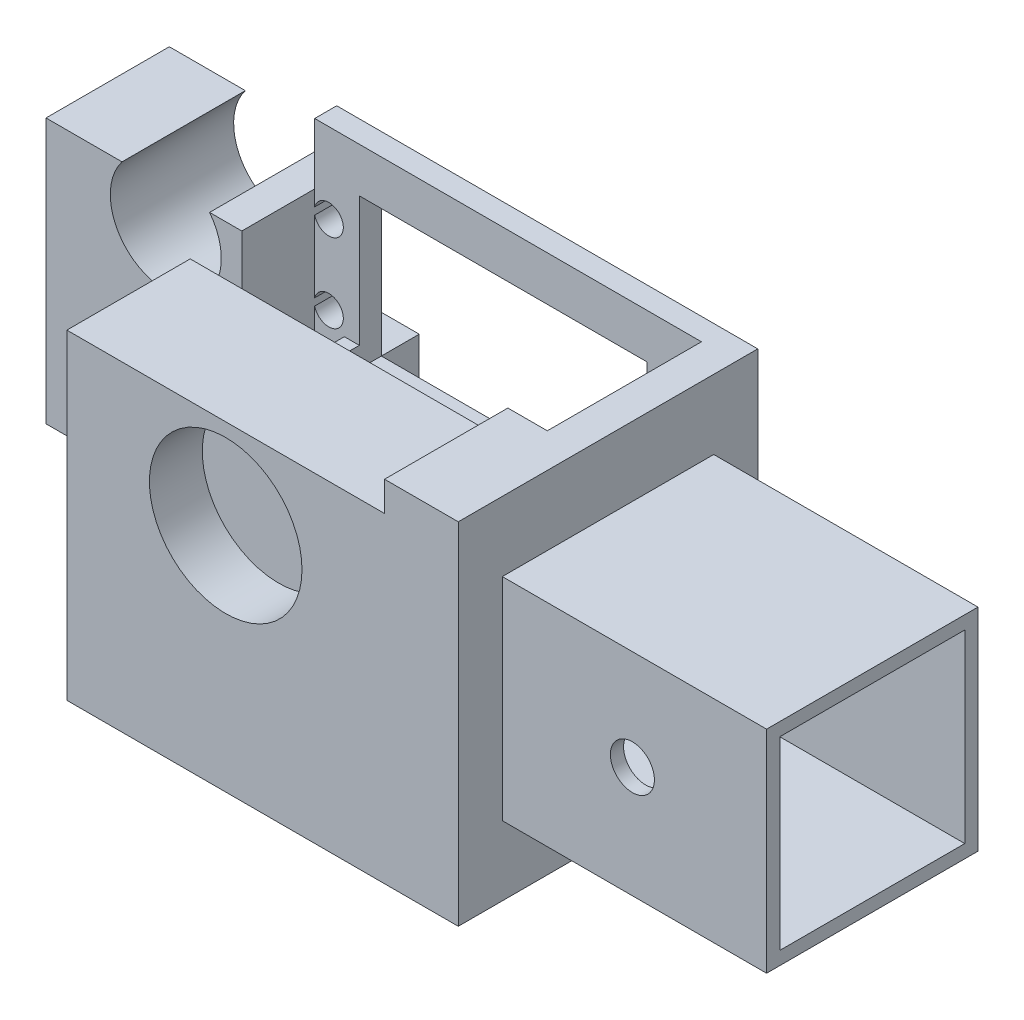
SolidWorks part; units mm, degrees
ref_plane "Front Plane" through (0, 0, 0) normal (0, 0, 1) x (1, 0, 0)
ref_plane "Top Plane" through (0, 0, 0) normal (0, 1, 0) x (1, 0, 0)
ref_plane "Right Plane" through (0, 0, 0) normal (1, 0, 0) x (0, 0, -1)
sketch "Sketch1" plane through (0, 0, 0) normal (0, 0, 1) x (1, 0, 0)
  line L1 (27.178, 17.2339) -> (-27.178, 17.2339)
  line L2 (27.178, 17.2339) -> (27.178, -17.2339)
  line L3 (27.178, -17.2339) -> (-27.178, -17.2339)
  line L4 (-27.178, 17.2339) -> (-27.178, -17.2339)
  line L5 (27.178, 17.2339) -> (-27.178, -17.2339) construction
  line L6 (27.178, -17.2339) -> (-27.178, 17.2339) construction
  line L7 (-27.178, 0) -> (-20.1041, 0) construction
  line L8 (-20.1041, 10.16) -> (-20.1041, -10.16) construction
  line L9 (0, 17.2339) -> (0, 10.16) construction
  line L10 (20.1041, 10.16) -> (-20.1041, 10.16) construction
  line L11 (-27.178, -5.1649) -> (-27.178, 5.1649) construction
  line L13 (20.1041, -10.16) -> (-20.1041, -10.16)
  line L14 (20.1041, -10.16) -> (20.1041, 10.16)
  line L15 (20.1041, 10.16) -> (-20.1041, 10.16)
  line L16 (-20.1041, -10.16) -> (-20.1041, 10.16)
  line L17 (20.1041, -10.16) -> (-20.1041, 10.16) construction
  line L18 (20.1041, 10.16) -> (-20.1041, -10.16) construction
  point P0 (0, 0)
  point P16 (0, 0)
extrude "Boss-Extrude1" add sketch "Sketch1" against normal up to surface (27.94 mm away)
sketch "Sketch2" plane through (0, 0, 0) normal (0, 0, 1) x (1, 0, 0)
  line L0 (20.1041, 10.16) -> (-20.1041, 10.16) construction
  line L1 (22.8981, -12.954) -> (-22.8981, -12.954)
  line L2 (22.8981, -12.954) -> (22.8981, 12.954)
  line L3 (22.8981, 12.954) -> (-22.8981, 12.954)
  line L4 (-22.8981, -12.954) -> (-22.8981, 12.954)
  line L5 (22.8981, -12.954) -> (-22.8981, 12.954) construction
  line L6 (22.8981, 12.954) -> (-22.8981, -12.954) construction
  line L7 (27.178, 17.2339) -> (-27.178, 17.2339)
  line L8 (27.178, 17.2339) -> (27.178, -17.2339)
  line L9 (27.178, -17.2339) -> (-27.178, -17.2339)
  line L10 (-27.178, 17.2339) -> (-27.178, -17.2339)
  line L11 (27.178, 17.2339) -> (-27.178, -17.2339) construction
  line L12 (27.178, -17.2339) -> (-27.178, 17.2339) construction
  line L13 (-20.1041, 10.16) -> (-20.1041, -10.16) construction
  point P0 (0, 0)
  point P6 (0, 0)
  dimension "D1" = 2.794
  dimension "D2" = 2.794
extrude "Cut-Extrude1" cut sketch "Sketch2" against normal offset from surface (24.765 mm away) 3.175 up to face at (0, 0, -27.94)
sketch "Sketch3" plane through (0, 0, -27.94) normal (0, 0, -1) x (-1, 0, 0)
  circle A0 centre (-25.146, 5.6769) radius 2.0497
  circle A1 centre (-25.146, -5.6769) radius 2.0955
  circle A2 centre (25.146, -5.6769) radius 2.0955
  circle A3 centre (25.146, 5.6769) radius 2.0955
extrude "Cut-Extrude2" cut sketch "Sketch3" against normal through all
sketch "Sketch4" plane through (22.8981, 0, 0) normal (1, 0, 0) x (0, 0, -1)
  line L0 (0, -12.954) -> (0, 12.954) construction
  line L1 (2.54, 4.7625) -> (21.59, 4.7625)
  line L2 (2.54, 4.7625) -> (2.54, -4.7625)
  line L3 (2.54, -4.7625) -> (21.59, -4.7625)
  line L4 (21.59, 4.7625) -> (21.59, -4.7625)
  point P4 (2.54, 0)
  dimension "D1" = 19.05
  dimension "D2" = 9.525
  dimension "D3" = 2.54
extrude "Cut-Extrude3" cut sketch "Sketch4" against normal blind 12.7
sketch "Sketch5" plane through (0, 0, 0) normal (0, 0, 1) x (1, 0, 0)
  line L1 (-22.8981, 12.954) -> (22.8981, 12.954)
  line L2 (-22.8981, 12.954) -> (-22.8981, -12.954)
  line L3 (-22.8981, -12.954) -> (22.8981, -12.954)
  line L4 (22.8981, 12.954) -> (22.8981, -12.954)
extrude "Boss-Extrude2" add sketch "Sketch5" along normal blind 2.54
sketch "Sketch6" plane through (0, 0, 2.54) normal (0, 0, 1) x (1, 0, 0)
  line L11 (-22.8981, -12.954) -> (22.8981, -12.954) construction
  line L12 (-12.7, -12.954) -> (12.7, -12.954)
  line L13 (-12.7, -12.954) -> (-12.7, -17.2339)
  line L14 (-12.7, -17.2339) -> (12.7, -17.2339)
  line L15 (12.7, -12.954) -> (12.7, -17.2339)
  line L16 (-27.178, -17.2339) -> (27.178, -17.2339) construction
  point P0 (0, -12.954)
  dimension "D1" = 25.4
extrude "Boss-Extrude3" add sketch "Sketch6" against normal up to surface (27.305 mm away) up to face at (0.0038, 0, -24.765)
sketch "Sketch7" plane through (0, 0, 2.54) normal (0, 0, 1) x (1, 0, 0)
  line L1 (-12.7, -17.2339) -> (12.7, -17.2339)
  line L2 (-12.7, -17.2339) -> (-12.7, -10.8839)
  line L3 (-12.7, -10.8839) -> (12.7, -10.8839)
  line L4 (12.7, -17.2339) -> (12.7, -10.8839)
  dimension "D1" = 25.4
  dimension "D2" = 6.35
extrude "Boss-Extrude4" add sketch "Sketch7" along normal blind 19.05
sketch "Sketch10" plane through (0, -10.8839, 0) normal (0, 1, 0) x (1, 0, 0)
  line L0 (22.8981, -2.54) -> (-22.8981, -2.54) construction
  line L1 (12.7, -21.59) -> (9.525, -21.59)
  line L2 (12.7, -21.59) -> (12.7, -2.54)
  line L3 (12.7, -2.54) -> (9.525, -2.54)
  line L4 (9.525, -21.59) -> (9.525, -2.54)
  line L6 (-12.7, -21.59) -> (-9.525, -21.59)
  line L7 (-12.7, -21.59) -> (-12.7, -2.54)
  line L8 (-12.7, -2.54) -> (-9.525, -2.54)
  line L9 (-9.525, -21.59) -> (-9.525, -2.54)
  dimension "D1" = 3.175
extrude "Boss-Extrude5" add sketch "Sketch10" along normal blind 19.05
chamfer "Chamfer1" distance 19.05 angle 45 2 edges at (-11.1125, 8.1661, 21.59) (11.1125, 8.1661, 21.59)
sketch "Sketch12" plane through (0, -17.2339, 0) normal (0, -1, 0) x (1, 0, 0)
  line L1 (-3.81, 3.81) -> (3.81, 3.81)
  line L2 (-3.81, 3.81) -> (-3.81, -27.94)
  line L3 (-3.81, -27.94) -> (3.81, -27.94)
  line L4 (3.81, 3.81) -> (3.81, -27.94)
  line L5 (-27.178, -27.94) -> (27.178, -27.94) construction
  point P8 (0, 3.81)
  dimension "D1" = 7.62
  dimension "D2" = 31.75
extrude "Boss-Extrude6" add sketch "Sketch12" along normal blind 3.175
sketch "Sketch13" plane through (0, 0, -27.94) normal (0, 0, -1) x (-1, 0, 0)
  line L0 (-20.1041, 10.16) -> (20.1041, 10.16) construction
  line L1 (20.7391, -10.795) -> (-20.7391, -10.795)
  line L2 (20.7391, -10.795) -> (20.7391, 10.795)
  line L3 (20.7391, 10.795) -> (-20.7391, 10.795)
  line L4 (-20.7391, -10.795) -> (-20.7391, 10.795)
  line L5 (20.7391, -10.795) -> (-20.7391, 10.795) construction
  line L6 (20.7391, 10.795) -> (-20.7391, -10.795) construction
  line L7 (-20.1041, -10.16) -> (-20.1041, 10.16) construction
  point P0 (0, 0)
  dimension "D1" = 0.635
  dimension "D2" = 0.635
extrude "Cut-Extrude7" cut sketch "Sketch13" against normal offset from surface (27.94 mm away) 2.54 up to face at (0, -1.251, 2.54)
sketch "Sketch14" plane through (-22.8981, 0, 0) normal (-1, 0, 0) x (0, 0, 1)
  line L0 (21.59, -10.8839) -> (21.59, -17.2339) construction
  line L5 (-24.765, 12.954) -> (-2.54, 12.954)
  line L6 (-24.765, 12.954) -> (-24.765, -7.874)
  line L7 (-24.765, -7.874) -> (-2.54, -7.874)
  line L8 (-2.54, 12.954) -> (-2.54, -7.874)
  line L9 (2.54, 12.954) -> (2.54, -12.954) construction
  line L10 (-24.765, -12.954) -> (2.54, -12.954) construction
  line L11 (-27.94, -20.4089) -> (21.59, -20.4089)
  line L12 (-27.94, -20.4089) -> (-27.94, -12.954)
  line L13 (-27.94, -12.954) -> (21.59, -12.954)
  line L14 (21.59, -20.4089) -> (21.59, -12.954)
  dimension "D1" = 5.08
  dimension "D2" = 5.08
extrude "Cut-Extrude8" cut sketch "Sketch14" against normal through all
sketch "Sketch15" plane through (-27.178, 0, 0) normal (-1, 0, 0) x (0, 0, 1)
  line L1 (-24.765, -12.954) -> (-27.94, -12.954)
  line L2 (-24.765, -12.954) -> (-24.765, -17.2339)
  line L3 (-24.765, -17.2339) -> (-27.94, -17.2339)
  line L4 (-27.94, -12.954) -> (-27.94, -17.2339)
extrude "Cut-Extrude9" cut sketch "Sketch15" against normal through all
sketch "Sketch16" plane through (0, -12.954, 0) normal (0, -1, 0) x (1, 0, 0)
  line L0 (27.178, -27.94) -> (-27.178, -27.94) construction
  line L1 (-22.8981, 2.54) -> (22.8986, 2.54)
  line L2 (-22.8981, 2.54) -> (-22.8981, -27.94)
  line L3 (-22.8981, -27.94) -> (22.8986, -27.94)
  line L4 (22.8986, 2.54) -> (22.8986, -27.94)
extrude "Boss-Extrude7" add sketch "Sketch16" along normal blind 20.32
sketch "Sketch17" plane through (0, 0, -27.94) normal (0, 0, -1) x (-1, 0, 0)
  line L0 (22.8981, -12.954) -> (27.178, -12.954) construction
  line L1 (22.8981, -12.954) -> (58.928, -12.954)
  line L2 (22.8981, -12.954) -> (22.8981, -33.274)
  line L3 (22.8981, -33.274) -> (58.928, -33.274)
  line L4 (58.928, -12.954) -> (58.928, -33.274)
  line L5 (22.8981, -33.274) -> (22.8981, -12.954) construction
  line L6 (27.178, -6.1889) -> (27.178, -12.954) construction
  line L7 (22.8981, -33.274) -> (-22.8986, -33.274) construction
  dimension "D1" = 31.75
extrude "Boss-Extrude8" add sketch "Sketch17" along normal blind 7.62 and the other way blind 10.16 separate body
sketch "Sketch18" plane through (0, -12.954, 0) normal (0, 1, 0) x (1, 0, 0)
  line L0 (-58.928, 17.78) -> (-22.8981, 17.78) construction
  line L1 (-58.928, 35.56) -> (-30.701, 35.56)
  line L2 (-58.928, 35.56) -> (-58.928, 17.78)
  line L3 (-58.928, 17.78) -> (-30.701, 17.78)
  line L4 (-30.701, 35.56) -> (-30.701, 17.78)
extrude "Boss-Extrude9" add sketch "Sketch18" along normal blind 17.8712
sketch "Sketch19" plane through (0, 0, -35.56) normal (0, 0, -1) x (-1, 0, 0)
  line L0 (27.178, 5.1649) -> (27.178, -5.1649) construction
  circle A0 centre (41.656, 0) radius 8.001
  point P4 (27.178, 0)
  dimension "D1" = 16.002
  dimension "D2" = 14.478
extrude "Cut-Extrude10" cut sketch "Sketch19" against normal up to next (17.78 mm away)
sketch "Sketch20" plane through (-22.8981, 0, 0) normal (-1, 0, 0) x (0, 0, 1)
  line L0 (2.54, 8.1661) -> (2.54, -12.954) construction
  line L1 (2.54, 8.1661) -> (21.59, 8.1661)
  line L2 (2.54, 8.1661) -> (2.54, -12.954)
  line L3 (2.54, -12.954) -> (21.59, -12.954)
  line L4 (21.59, 8.1661) -> (21.59, -12.954)
  line L5 (21.59, -10.8839) -> (2.54, 8.1661) construction
extrude "Cut-Extrude11" cut sketch "Sketch20" against normal through all
sketch "Sketch21" plane through (0, 0, 2.54) normal (0, 0, 1) x (1, 0, 0)
  line L1 (22.8986, -33.274) -> (-22.8981, -33.274)
  line L2 (22.8986, -33.274) -> (22.8986, 12.954)
  line L3 (22.8986, 12.954) -> (-22.8981, 12.954)
  line L4 (-22.8981, -33.274) -> (-22.8981, 12.954)
extrude "Boss-Extrude10" add sketch "Sketch21" along normal blind 12.7
sketch "Sketch23" plane through (0, 0, 15.24) normal (0, 0, 1) x (1, 0, 0)
  line L0 (22.8986, 12.954) -> (-22.8981, 12.954) construction
  circle A0 centre (0.0003, 0) radius 10.9982
  circle A3 centre (-41.656, 0) radius 8.4582 construction
  point P4 (0.0003, 12.954)
  dimension "D1" = 21.9964
extrude "Cut-Extrude12" cut sketch "Sketch23" against normal blind 7.62
sketch "Sketch25" plane through (0, 0, -27.94) normal (0, 0, -1) x (-1, 0, 0)
  line L0 (-22.8986, -33.274) -> (-22.8986, -12.954) construction
  line L1 (-27.178, 17.2339) -> (-33.528, 17.2339)
  line L2 (-27.178, 17.2339) -> (-27.178, 9.6139)
  line L3 (-27.178, 9.6139) -> (-33.528, 9.6139)
  line L4 (-33.528, 17.2339) -> (-33.528, 9.6139)
  line L5 (-22.8986, -33.274) -> (-33.528, -33.274)
  line L6 (-22.8986, -33.274) -> (-22.8986, -8.1661)
  line L7 (-22.8986, -8.1661) -> (-33.528, -8.1661)
  line L8 (-33.528, -33.274) -> (-33.528, -8.1661)
  line L9 (-27.178, -12.954) -> (-27.178, -6.1889) construction
  line L10 (22.8981, -33.274) -> (-22.8986, -33.274) construction
  dimension "D1" = 7.62
  dimension "D3" = 6.35
  dimension "D4" = 6.35
  dimension "D5" = 17.78
extrude "Boss-Extrude12" add sketch "Sketch25" against normal up to surface (3.175 mm away) up to face at (1.0926, -1.9147, -24.765)
sketch "Sketch26" plane through (0, 0, 15.24) normal (0, 0, 1) x (1, 0, 0)
  line L1 (22.8986, -33.274) -> (33.528, -33.274)
  line L2 (22.8986, -33.274) -> (22.8986, 17.2339)
  line L3 (22.8986, 17.2339) -> (33.528, 17.2339)
  line L4 (33.528, -33.274) -> (33.528, 17.2339)
extrude "Boss-Extrude14" add sketch "Sketch26" against normal up to surface (17.78 mm away) up to face at (0, 2.0002, -2.54)
sketch "Sketch27" plane through (0, 0, -24.765) normal (0, 0, 1) x (1, 0, 0)
  line L0 (33.528, 17.2339) -> (-27.178, 17.2339) construction
  line L1 (33.528, -33.274) -> (28.5856, -33.274)
  line L2 (33.528, -33.274) -> (33.528, 17.2339)
  line L3 (33.528, 17.2339) -> (28.5856, 17.2339)
  line L4 (28.5856, -33.274) -> (28.5856, 17.2339)
extrude "Boss-Extrude15" add sketch "Sketch27" along normal up to surface and the other way up to surface
sketch "Sketch28" plane through (0, -7.874, 0) normal (0, 1, 0) x (1, 0, 0)
  line L1 (20.7391, 24.765) -> (28.5856, 24.765)
  line L2 (20.7391, 24.765) -> (20.7391, 2.54)
  line L3 (20.7391, 2.54) -> (28.5856, 2.54)
  line L4 (28.5856, 24.765) -> (28.5856, 2.54)
extrude "Boss-Extrude16" add sketch "Sketch28" against normal up to surface (25.4 mm away) up to face at (5.3149, -33.274, -6.35)
sketch "Sketch29" plane through (33.528, 0, 0) normal (1, 0, 0) x (0, 0, -1)
  line L0 (-15.24, 17.2339) -> (27.94, 17.2339) construction
  line L1 (-8.89, 7.22) -> (21.59, 7.22)
  line L2 (-8.89, 7.22) -> (-8.89, -23.26)
  line L3 (-8.89, -23.26) -> (21.59, -23.26)
  line L4 (21.59, 7.22) -> (21.59, -23.26)
  line L5 (-15.24, -33.274) -> (-15.24, 17.2339) construction
  point P4 (6.35, 7.22)
  point P7 (6.35, 17.2339)
  point P8 (21.59, -8.02)
  point P11 (-15.24, -8.02)
  dimension "D1" = 30.48
  dimension "D2" = 30.48
extrude "Boss-Extrude17" add sketch "Sketch29" along normal blind 38.1
sketch "Sketch30" plane through (71.628, 0, 0) normal (1, 0, 0) x (0, 0, -1)
  line L0 (21.59, 7.22) -> (-8.89, 7.22) construction
  line L1 (-6.985, 5.315) -> (19.685, 5.315)
  line L2 (-6.985, 5.315) -> (-6.985, -21.355)
  line L3 (-6.985, -21.355) -> (19.685, -21.355)
  line L4 (19.685, 5.315) -> (19.685, -21.355)
  line L5 (-8.89, 7.22) -> (-8.89, -23.26) construction
  point P4 (6.35, 5.315)
  point P7 (6.35, 7.22)
  point P10 (-8.89, -8.02)
  point P11 (-6.985, -8.02)
  dimension "D1" = 26.67
  dimension "D2" = 26.67
extrude "Cut-Extrude13" cut sketch "Sketch30" against normal blind 38.1
sketch "Sketch31" plane through (0, 0, -21.59) normal (0, 0, -1) x (-1, 0, 0)
  circle A0 centre (-52.2811, -7.2021) radius 3.175
extrude "Cut-Extrude14" cut sketch "Sketch31" against normal through all
